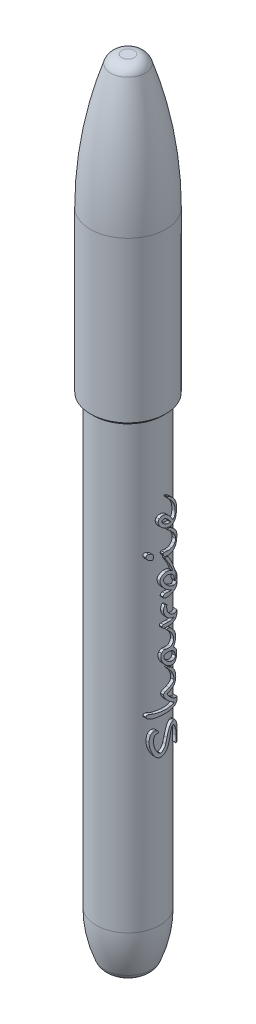
SolidWorks part; units mm, degrees
ref_plane "Front Plane" through (0, 0, 0) normal (0, 0, 1) x (1, 0, 0)
ref_plane "Top Plane" through (0, 0, 0) normal (0, 1, 0) x (1, 0, 0)
ref_plane "Right Plane" through (0, 0, 0) normal (1, 0, 0) x (0, 0, -1)
sketch "Sketch1" plane through (0, 0, 0) normal (0, 0, 1) x (1, 0, 0)
  line L0 (0, 0) -> (0, 145.4469) construction
  line L1 (5.5, 85) -> (5.5, 8.6106)
  line L2 (0, 0) -> (3.5, 0)
  line L3 (5.5, 85) -> (6.5, 85)
  line L4 (6.5, 85) -> (6.5, 113.071)
  line L5 (0, 136) -> (2.5, 136)
  line L6 (0, 0) -> (0, 136)
  arc A0 (5.5, 8.6106) -> (3.5, 0) centre (-14.0355, 8.6106) cw
  arc A1 (6.5, 113.071) -> (2.5, 136) centre (-61.2176, 113.071) ccw
  dimension "D1" = 3.5
  dimension "D3" = 2.5
  dimension "D4" = 6.5
  dimension "D2" = 85
  dimension "D5" = 51
  dimension "D6" = 5.5
revolve "Revolve1" add sketch "Sketch1" angle 360 about L0
fillet "Fillet1" radius 2 1 edges at (0, 136, -2.5)
fillet "Fillet2" radius 2 1 edges at (0, 0, -3.5)
chamfer "Chamfer1" distance 0.5 angle 45 1 edges at (0, 85, -6.5)
surface "Surface-Offset1" parameters "D1"=0.5
sketch "Sketch2" plane through (0, 0, 0) normal (1, 0, 0) x (0, 0, -1)
  line L0 (3.6056, 71.2466) -> (3.6056, 33.3652) construction
  text T0 "Sharpie" font "Segoe Script" height in points 22
extrude "Boss-Extrude1" add sketch "Sketch2" along normal up to surface (5.9229 mm away)
